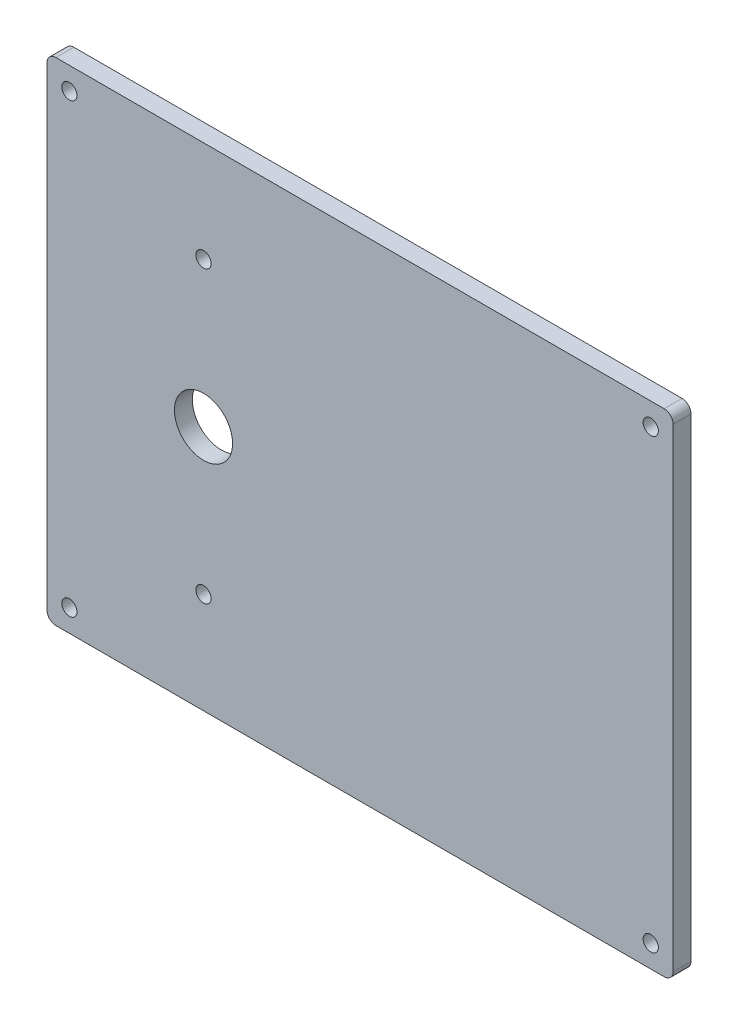
SolidWorks part; units mm, degrees
ref_plane "Front Plane" through (0, 0, 0) normal (0, 0, 1) x (1, 0, 0)
ref_plane "Top Plane" through (0, 0, 0) normal (0, 1, 0) x (1, 0, 0)
ref_plane "Right Plane" through (0, 0, 0) normal (1, 0, 0) x (0, 0, -1)
sketch "Sketch1" plane through (0, 0, 0) normal (0, 0, 1) x (1, 0, 0)
  line L1 (-1.1094, 68.5389) -> (138.8906, 68.5389)
  line L2 (-1.1094, 68.5389) -> (-1.1094, -41.4611)
  line L3 (-1.1094, -41.4611) -> (138.8906, -41.4611)
  line L4 (138.8906, 68.5389) -> (138.8906, -41.4611)
  dimension "D1" = 110
  dimension "D2" = 140
extrude "Boss-Extrude1" add sketch "Sketch1" along normal blind 4
sketch "Sketch2" plane through (0, 0, 0) normal (0, 0, -1) x (-1, 0, 0)
  line L0 (1.1094, -41.4611) -> (-138.8906, -41.4611) construction
  line L1 (1.1094, 68.5389) -> (1.1094, -41.4611) construction
  line L2 (-138.8906, 68.5389) -> (1.1094, 68.5389) construction
  line L4 (-138.8906, -41.4611) -> (-138.8906, 68.5389) construction
  circle A0 centre (-133.8906, 63.5389) radius 1.7
  circle A1 centre (-3.8906, 63.5389) radius 1.7
  circle A2 centre (-133.8906, -36.4611) radius 1.7
  circle A3 centre (-3.8906, -36.4611) radius 1.7
  circle A4 centre (-33.8906, 13.5389) radius 6.5
  circle A5 centre (-116.8906, 13.5389) radius 20
  circle A6 centre (-3.8906, 13.5389) radius 1.6
  circle A7 centre (-33.8906, -18.8911) radius 1.7
  circle A8 centre (-33.8906, 45.9689) radius 1.7
  dimension "D1" = 5
  dimension "D9" = 13
  dimension "D12" = 3.4
  dimension "D13" = 3.4
  dimension "D14" = 3.4
  dimension "D15" = 3.4
  dimension "D16" = 40
  dimension "D17" = 35
  dimension "D18" = 55
  dimension "D19" = 5
  dimension "D21" = 32.43
  dimension "D22" = 32.43
  dimension "D23" = 3.4
  dimension "D2" = 5
  dimension "D3" = 5
  dimension "D4" = 5
  dimension "D5" = 5
  dimension "D6" = 5
  dimension "D7" = 5
  dimension "D8" = 5
  dimension "D10" = 22
  dimension "D11" = 83
  dimension "D20" = 55
extrude "Cut-Extrude1" cut sketch "Sketch2" against normal blind 4 contours A4 | A8 | A7 | A3 | A2 | A0 | A1 region at (133.8906, 63.5389, 0) region at (3.8906, 63.5389, 0) region at (133.8906, -36.4611, 0) region at (3.8906, -36.4611, 0) region at (33.8906, 13.5389, 0) region at (33.8906, -18.8911, 0) region at (33.8906, 45.9689, 0)
fillet "Fillet1" radius 2 4 edges at (138.8906, -41.4611, 2) (-1.1094, -41.4611, 2) (-1.1094, 68.5389, 2) (138.8906, 68.5389, 2)
